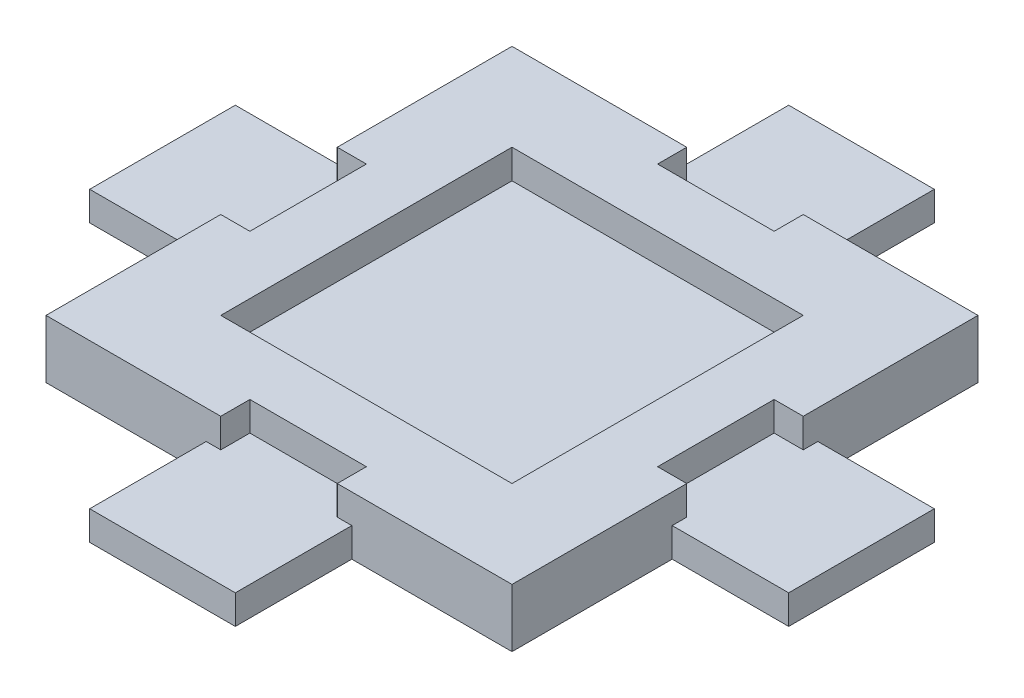
SolidWorks part; units mm, degrees
material "6061 Alloy"
ref_plane "Front Plane" through (0, 0, 0) normal (0, 0, 1) x (1, 0, 0)
ref_plane "Top Plane" through (0, 0, 0) normal (0, 1, 0) x (1, 0, 0)
ref_plane "Right Plane" through (0, 0, 0) normal (1, 0, 0) x (0, 0, -1)
sketch "Sketch1" plane through (0, 0, 0) normal (0, 1, 0) x (1, 0, 0)
  line L1 (0, 0) -> (101.6, 0)
  line L2 (0, 0) -> (0, 101.6)
  line L3 (0, 101.6) -> (101.6, 101.6)
  line L4 (101.6, 0) -> (101.6, 101.6)
  dimension "D1" = 101.6
  dimension "D2" = 101.6
extrude "Boss-Extrude1" add sketch "Sketch1" along normal blind 12.7
sketch "Sketch7" plane through (0, 12.7, 0) normal (0, 1, 0) x (1, 0, 0)
  line L0 (0, 101.6) -> (0, 0) construction
  line L1 (19.05, 82.55) -> (82.55, 82.55)
  line L2 (19.05, 82.55) -> (19.05, 19.05)
  line L3 (19.05, 19.05) -> (82.55, 19.05)
  line L4 (82.55, 82.55) -> (82.55, 19.05)
  line L5 (19.05, 82.55) -> (82.55, 19.05) construction
  line L6 (19.05, 19.05) -> (82.55, 82.55) construction
  line L7 (0, 0) -> (101.6, 0) construction
  point P0 (63.4968, 59.9004)
  point P7 (50.8, 82.55)
  point P10 (82.55, 50.8)
  dimension "D1" = 63.5
  dimension "D2" = 63.5
  dimension "D3" = 50.8
  dimension "D4" = 50.8
extrude "Cut-Extrude2" cut sketch "Sketch7" against normal blind 6.35
sketch "Sketch8" plane through (0, 12.7, 0) normal (0, 1, 0) x (1, 0, 0)
  line L0 (38.1, 101.6) -> (38.1, 95.25)
  line L1 (101.6, 101.6) -> (0, 101.6) construction
  line L2 (38.1, 95.25) -> (63.5, 95.25)
  line L3 (63.5, 95.25) -> (63.5, 101.6)
  line L4 (63.5, 101.6) -> (38.1, 101.6)
  point P6 (50.8, 101.6)
  dimension "D1" = 25.4
  dimension "D2" = 6.35
extrude "Cut-Extrude3" cut sketch "Sketch8" against normal blind 6.35
ref_point "Point4"
ref_axis "Axis3" through (50.8, 6.35, -50.8) along (0, 1, 0)
pattern_circular "CirPattern2" count 4 over 360 about axis through (50.8, 6.35, -50.8) along (0, 1, 0) of "Cut-Extrude3"
sketch "Sketch9" plane through (0, 12.7, 0) normal (0, 1, 0) x (1, 0, 0)
  line L1 (34.925, 101.6) -> (66.675, 101.6)
  line L2 (34.925, 101.6) -> (34.925, 127)
  line L3 (34.925, 127) -> (66.675, 127)
  line L4 (66.675, 101.6) -> (66.675, 127)
  line L9 (63.5, 101.6) -> (38.1, 101.6) construction
  dimension "D1" = 25.4
  dimension "D2" = 31.75
extrude "Boss-Extrude3" add sketch "Sketch9" against normal blind 6.35 from offset 6.35 offset against normal yes
pattern_circular "CirPattern3" count 4 over 360 about axis through (50.8, 6.35, -50.8) along (0, 1, 0) of "Boss-Extrude3"
